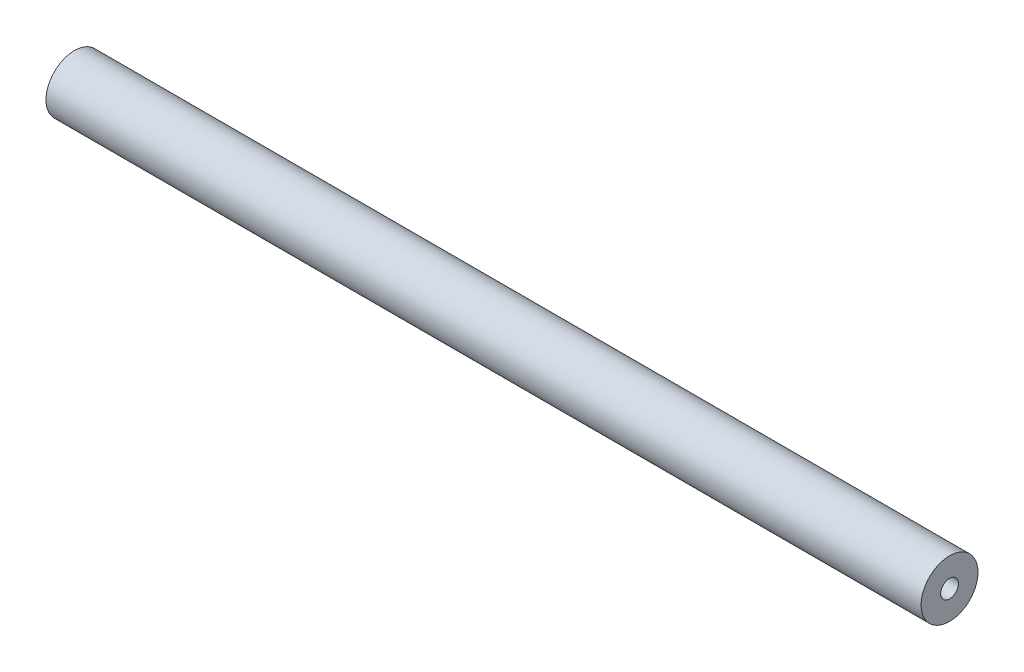
SolidWorks part; units mm, degrees
material "6061 합금"
ref_plane "정면" through (0, 0, 0) normal (0, 0, 1) x (1, 0, 0)
ref_plane "윗면" through (0, 0, 0) normal (0, 1, 0) x (1, 0, 0)
ref_plane "우측면" through (0, 0, 0) normal (1, 0, 0) x (0, 0, -1)
sketch "스케치2" plane through (0, 0, 0) normal (1, 0, 0) x (0, 0, -1)
  circle A0 centre (0, 0) radius 4
  dimension "D1" = 8
extrude "보스-돌출1" add sketch "스케치2" along normal up to surface (122.9935 mm away)
hole_wizard "M3x0.5 Tapped Hole1" positions "스케치3" profile "스케치4" tap size "M3x0.5" standard "ANSI Metric"
sketch "스케치3" plane through (0, 0, 0) normal (1, 0, 0) x (0, 0, -1)
  point P4 (0, 0)
  point P5 (0, 0)
sketch "스케치4" plane through (0, 0, 0) normal (0, 1, 0) x (0, 0, 1)
  line L0 (0, 0) -> (0, 22.2511)
  line L1 (0, 22.2511) -> (1.25, 21.5)
  line L2 (1.25, 21.5) -> (1.25, 0)
  line L5 (1.25, 0) -> (0, 0)
  line L10 (0, 22.2511) -> (-1.25, 21.5) construction
  line L11 (0, -6.35) -> (0, 107.95) construction
  dimension "탭 드릴 지름" = 2.5
  dimension "탭 드릴 깊이" = 21.5
  dimension "드릴 각도" = 118
cosmetic thread "Hole Thread1"
ref_plane "Plane1" through (61.4968, 0, 0) normal (-1, 0, 0) x (0, 0, 1)
mirror "대칭 복사1" about plane through (61.4968, 0, 0) normal (-1, 0, 0) of "M3x0.5 Tapped Hole1"
